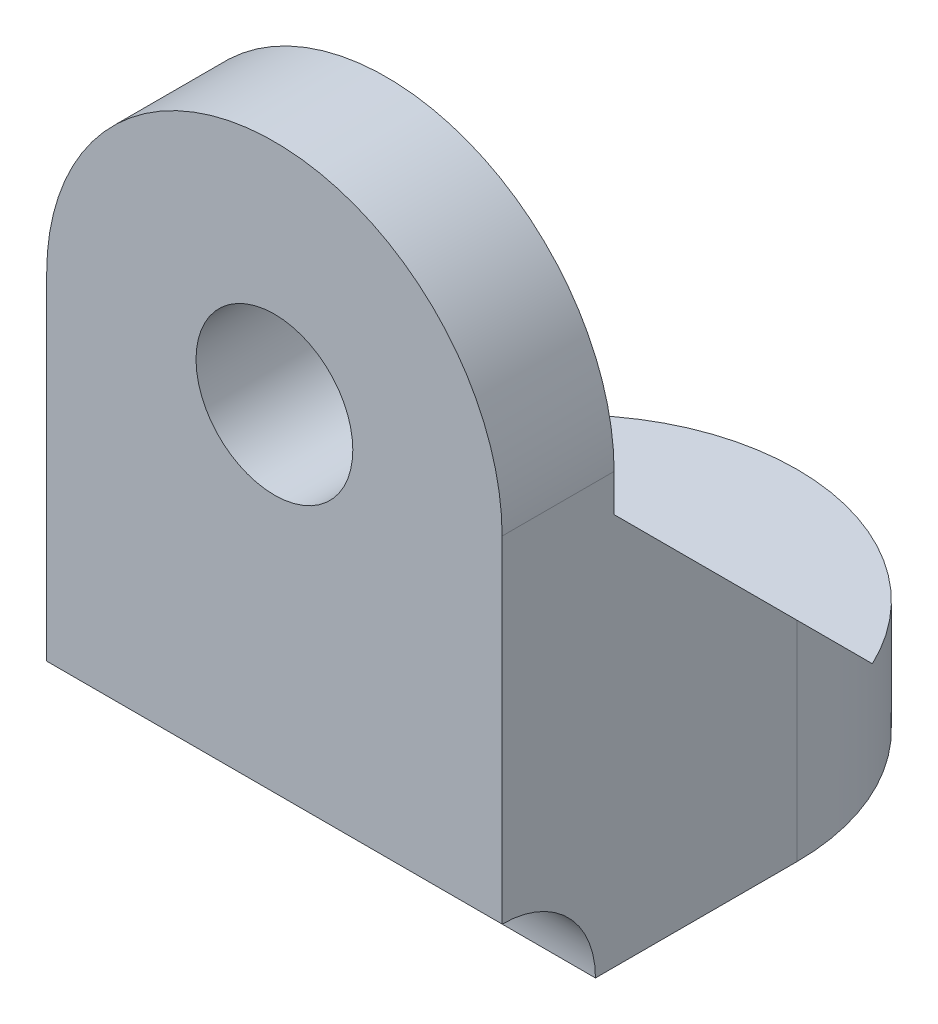
SolidWorks part; units mm, degrees
ref_plane "Спереди" through (0, 0, 0) normal (0, 0, 1) x (1, 0, 0)
ref_plane "Сверху" through (0, 0, 0) normal (0, 1, 0) x (1, 0, 0)
ref_plane "Справа" through (0, 0, 0) normal (1, 0, 0) x (0, 0, -1)
sketch "Эскиз1" plane through (0, 0, 0) normal (0, 0, 1) x (1, 0, 0)
  line L1 (-6.1, 0) -> (6.1, 0)
  line L2 (-6.1, 0) -> (-6.1, -11.5025)
  line L3 (-6.1, -11.5025) -> (6.1, -11.5025)
  line L4 (6.1, 0) -> (6.1, -11.5025)
  circle A0 centre (0, 0) radius 2.1
  circle A1 centre (0, 0) radius 6.1
  dimension "D1" = 4.2
  dimension "D3" = 11.5025
  dimension "D2" = 4
extrude "Бобышка-Вытянуть1" add sketch "Эскиз1" along normal blind 3 contours A1 L2 L3 L4 | L1 A1 A0 | L1 A1 A0 region at (0, 2.8172, 0) region at (0, -2.8172, 0) region at (0, -8.0086, 0)
sketch "Эскиз2" plane through (0, -11.5025, 0) normal (0, -1, 0) x (1, 0, 0)
  line L0 (6.1, 3) -> (6.1, 0) construction
  line L1 (-6.1, 3) -> (6.1, 3)
  line L2 (-6.1, 3) -> (-6.1, -11)
  line L3 (-6.1, -11) -> (6.1, -11)
  line L4 (6.1, 3) -> (6.1, -11)
  circle A0 centre (0, -4.9) radius 2.1
  circle A1 centre (0, -4.9) radius 6.1
  line M2 (-6.1, 0) -> (6.1, 0)
  line M3 (6.1, 0) -> (6.1, 3)
  line M4 (6.1, 3) -> (-6.1, 3)
  line M5 (-6.1, 3) -> (-6.1, 0)
  dimension "D2" = 4.2
  dimension "D3" = 4.9
extrude "Бобышка-Вытянуть2" add sketch "Эскиз2" against normal blind 3 contours A1 M2 M3 M4 M5 | A1 L2 M2 | A1 M2 | A1 L4 M2 | A1 A0 M2 region at (0, -11.5025, 1.6967) region at (-5.3952, -11.5025, -1.17) region at (5.3952, -11.5025, -1.17) region at (-5.3018, -11.5025, -2.2309) region at (0, -11.5025, 0.4843)
chamfer "Фаска1" distance 7.5 angle 45 1 edges at (0, -8.5025, 0)
sketch "Эскиз3" plane through (-6.1, 0, 0) normal (-1, 0, 0) x (0, 0, 1)
  circle A0 centre (3, -11.5025) radius 2.5
  dimension "D1" = 5
extrude "Вырез-Вытянуть1" cut sketch "Эскиз3" against normal through all
